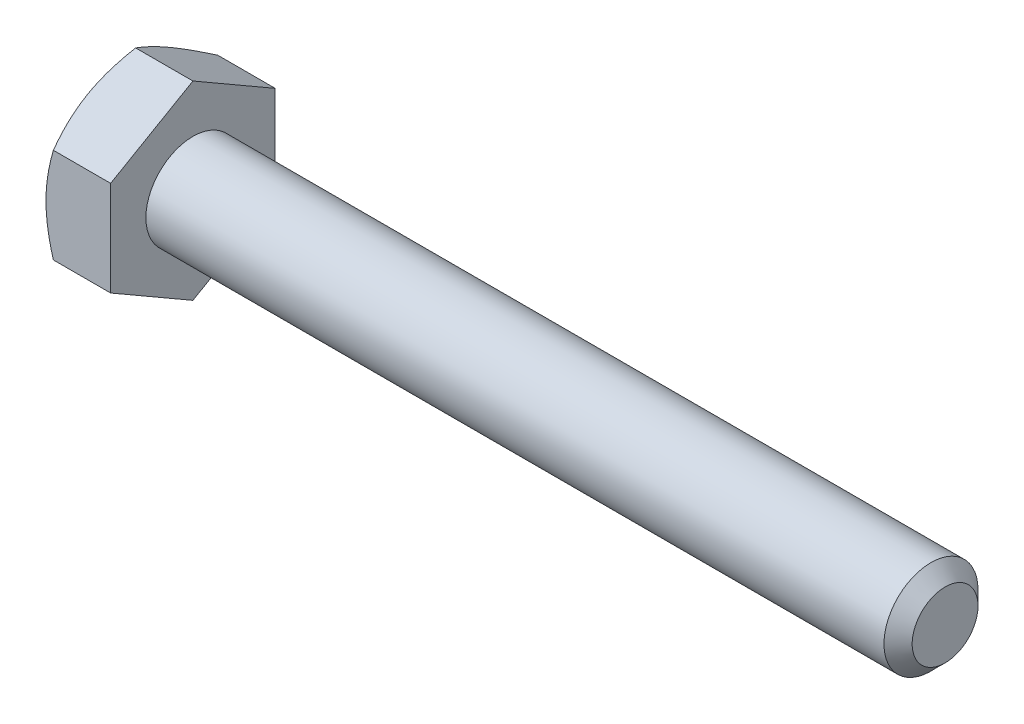
SolidWorks part; units mm, degrees
ref_plane "Front Plane" through (0, 0, 0) normal (0, 0, 1) x (1, 0, 0)
ref_plane "Top Plane" through (0, 0, 0) normal (0, 1, 0) x (1, 0, 0)
ref_plane "Right Plane" through (0, 0, 0) normal (1, 0, 0) x (0, 0, -1)
sketch "Sketch1" plane through (0, 0, 0) normal (0, 0, 1) x (1, 0, 0)
  line L0 (-27.5828, 0) -> (27.5828, 0) construction
  line L1 (27.5828, 3.175) -> (27.5828, -3.175) construction
  line L2 (-23.2172, 5.5562) -> (-23.2172, -5.5562) construction
  line L3 (-27.5828, 5.5562) -> (-27.5828, -5.5562) construction
  point P9 (-23.2172, 0)
  point P10 (23.1378, -3.175)
  dimension "Screw Dia" = 6.35
  dimension "Hex" = 11.1125
  dimension "Head Ht" = 4.3656
  dimension "Screw Lenght" = 50.8
  dimension "D1" = 4.445
ref_plane "Plane2" through (27.5828, 0, 0) normal (1, 0, 0) x (0, 0, -1)
sketch "Sketch5" plane through (27.5828, 0, 0) normal (1, 0, 0) x (0, 0, -1)
  circle A0 centre (0, 0) radius 3.175
extrude "Boss-Extrude3" add sketch "Sketch5" against normal up to vertex (50.8 mm away) up to point (-23.2172, 0, 0)
sketch "Sketch9" plane through (27.5828, 0, 0) normal (1, 0, 0) x (0, 0, -1)
  circle A1 centre (0, 0) radius 3.175
  circle A2 centre (0, 0) radius 3.175
  dimension "D1" = 0
curve "Helix/Spiral1" pitch 1.27 height 20.32 turns 16 parameters "Pitch"=1.27
chamfer "Chamfer1" distance 0.9525 angle 45 1 edges at (27.5828, 0, -3.175)
sketch "Sketch10" plane through (0, 0, 0) normal (0, 0, 1) x (1, 0, 0)
  line L0 (27.5828, 3.175) -> (28.0591, 2.3501)
  line L1 (28.0591, 2.3501) -> (28.2178, 2.3501)
  line L2 (28.2178, 2.3501) -> (28.6941, 3.175)
  line L3 (27.5828, 3.175) -> (28.6941, 3.175)
  line L4 (28.1384, 3.175) -> (28.1384, 2.3501) construction
  line L5 (27.8209, 2.7626) -> (28.4559, 2.7626) construction
  dimension "D1" = 60
  dimension "D2" = 0.1588
  dimension "D3" = 0.635
sweep "Cut-Sweep1" [suppressed] cut profiles "Sketch10" path "Helix/Spiral1"
sketch "Sketch11" plane through (0, 0, 0) normal (0, 0, 1) x (1, 0, 0)
  line L0 (-23.2172, 3.175) -> (-23.2172, 0)
  line L1 (-23.2172, 0) -> (11.7078, 0)
  line L3 (11.7078, 0) -> (8.5328, 3.175)
  line L4 (-23.2172, 3.175) -> (8.5328, 3.175)
  dimension "D1" = 45
  dimension "MIn Thread" = 19.05
revolve "Revolve1" add sketch "Sketch11" angle 360 about L1
sketch "Sketch6" plane through (-23.2172, 0, 0) normal (-1, 0, 0) x (0, 0, 1)
  line L0 (0, 5.5562) -> (0, -5.5562) construction
  line L1 (5.5563, 3.2079) -> (0, 6.4158)
  line L2 (0, 6.4158) -> (-5.5563, 3.2079)
  line L3 (-5.5563, 3.2079) -> (-5.5563, -3.2079)
  line L4 (-5.5563, -3.2079) -> (0, -6.4158)
  line L5 (0, -6.4158) -> (5.5563, -3.2079)
  line L6 (5.5563, -3.2079) -> (5.5563, 3.2079)
  circle A0 centre (0, 0) radius 5.5563 construction
extrude "Boss-Extrude4" add sketch "Sketch6" along normal up to vertex (4.3656 mm away) up to point (-27.5828, -5.5562, 0)
sketch "Sketch7" plane through (-27.5828, 0, 0) normal (-1, 0, 0) x (0, 0, 1)
  circle A0 centre (0, 0) radius 5.5563 construction
  circle A1 centre (0, 0) radius 5.5563
sketch "Sketch8" plane through (-27.5828, 0, 0) normal (-1, 0, 0) x (0, 0, 1)
  circle A0 centre (0, 0) radius 5.5563 construction
  circle A1 centre (0, 0) radius 5.5563
extrude "Cut-Extrude3" cut sketch "Sketch8" against normal through all draft 60 flip side to cut
equation "\"D2@Sketch10\" = \"Pitch@Helix/Spiral1\"*.125"
equation "\"D3@Sketch10\" = \"Pitch@Helix/Spiral1\"*.5"
equation "\"D3@Helix/Spiral1\" = \"MIn Thread@Sketch11\"+\"Pitch@Helix/Spiral1\""
equation "\"D1@Chamfer1\" = \"Pitch@Helix/Spiral1\"*.75"
equation "\"D1@Sketch1\" = \"Pitch@Helix/Spiral1\"*3.5"
